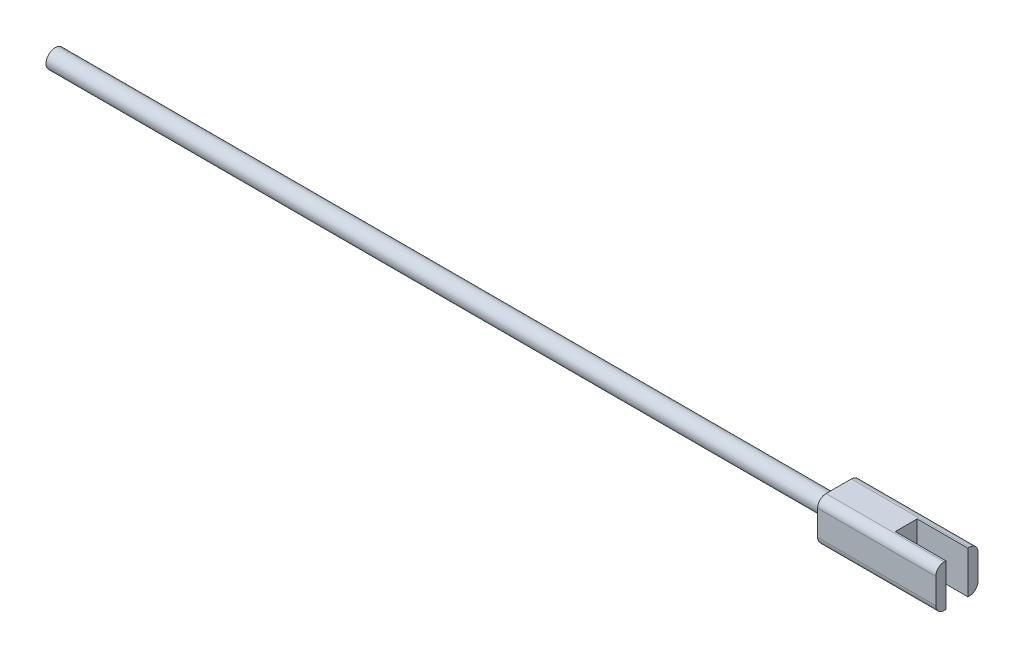
SolidWorks part; units mm, degrees
ref_plane "Front Plane" through (0, 0, 0) normal (0, 0, 1) x (1, 0, 0)
ref_plane "Top Plane" through (0, 0, 0) normal (0, 1, 0) x (1, 0, 0)
ref_plane "Right Plane" through (0, 0, 0) normal (1, 0, 0) x (0, 0, -1)
sketch "Sketch1" plane through (0, 0, 0) normal (1, 0, 0) x (0, 0, -1)
  circle A0 centre (0, 0) radius 1.09
extrude "Boss-Extrude1" add sketch "Sketch1" along normal blind 94.829
ref_plane "Plane1" through (92.829, 0, 0) normal (1, 0, 0) x (0, 0, -1)
sketch "Sketch2" plane through (92.829, 0, 0) normal (1, 0, 0) x (0, 0, -1)
  line L0 (-1.5, -2.5) -> (1.5, -2.5)
  line L1 (2.5, -1.5) -> (2.5, 1.5)
  line L2 (1.5, 2.5) -> (-1.5, 2.5)
  line L3 (-2.5, 1.5) -> (-2.5, -1.5)
  arc A0 (1.5, -2.5) -> (2.5, -1.5) centre (1.5, -1.5) ccw
  arc A1 (2.5, 1.5) -> (1.5, 2.5) centre (1.5, 1.5) ccw
  arc A2 (-1.5, 2.5) -> (-2.5, 1.5) centre (-1.5, 1.5) ccw
  arc A3 (-2.5, -1.5) -> (-1.5, -2.5) centre (-1.5, -1.5) ccw
extrude "Boss-Extrude2" add sketch "Sketch2" along normal blind 14
sketch "Sketch3" plane through (0, 0, 0) normal (0, 1, 0) x (1, 0, 0)
  line L0 (100.829, 1.3) -> (107.829, 1.3)
  line L1 (107.829, 1.3) -> (107.829, -1.3)
  line L2 (107.829, -1.3) -> (100.829, -1.3)
  line L3 (100.829, -1.3) -> (100.829, 1.3)
extrude "Cut-Extrude1" cut sketch "Sketch3" against normal through all and the other way through all
